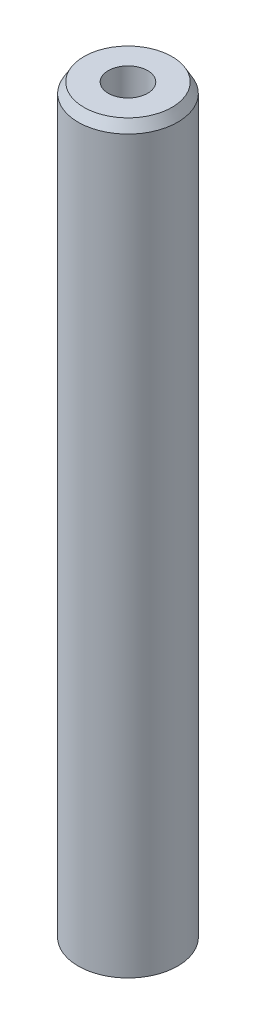
SolidWorks part; units mm, degrees
ref_plane "Front Plane" through (0, 0, 0) normal (0, 0, 1) x (1, 0, 0)
ref_plane "Top Plane" through (0, 0, 0) normal (0, 1, 0) x (1, 0, 0)
ref_plane "Right Plane" through (0, 0, 0) normal (1, 0, 0) x (0, 0, -1)
sketch "Sketch1" plane through (0, 0, 0) normal (0, 1, 0) x (1, 0, 0)
  circle A0 centre (0, 0) radius 15
  dimension "SHAFT_OD" = 30
extrude "Boss-Extrude1" add sketch "Sketch1" along normal blind 224.992
sketch "Sketch2" plane through (0, 0, 0) normal (0, 1, 0) x (1, 0, 0)
  circle A0 centre (0, 0) radius 5.9333
  dimension "BORE_D" = 11.8666
extrude "Cut-Extrude1" cut sketch "Sketch2" along normal through all
chamfer "Chamfer1" distance 3.011 angle 29.933 2 edges at (0, 224.992, 15) (0, 0, 15) first distance on face at (0, 224.992, 15) first distance on face at (0, 0, 5.9333)
